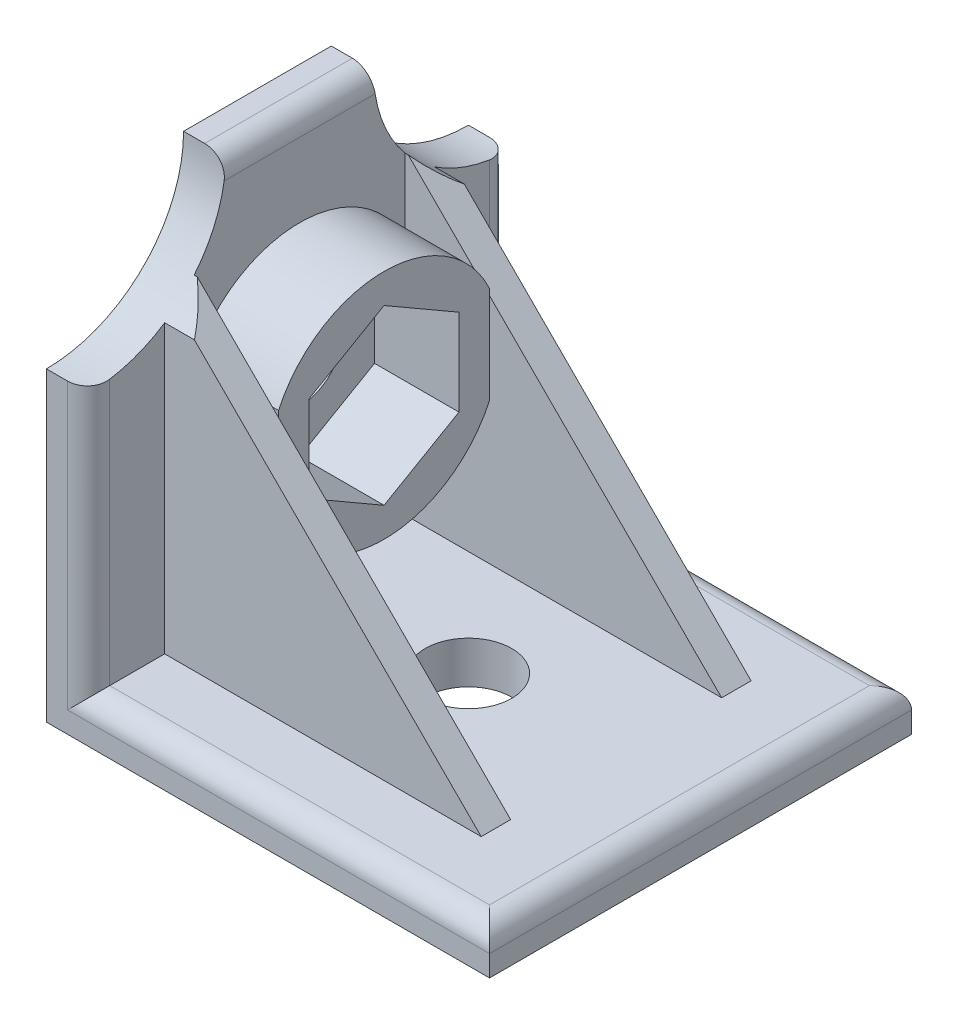
SolidWorks part; units mm, degrees
ref_plane "Plan de face" through (0, 0, 0) normal (0, 0, 1) x (1, 0, 0)
ref_plane "Plan de dessus" through (0, 0, 0) normal (0, 1, 0) x (1, 0, 0)
ref_plane "Plan de droite" through (0, 0, 0) normal (1, 0, 0) x (0, 0, -1)
sketch "Esquisse1" plane through (0, 0, 0) normal (0, 1, 0) x (1, 0, 0)
  line L1 (10.5, -10) -> (-10.5, -10)
  line L2 (10.5, -10) -> (10.5, 10)
  line L3 (10.5, 10) -> (-10.5, 10)
  line L4 (-10.5, -10) -> (-10.5, 10)
  line L5 (10.5, -10) -> (-10.5, 10) construction
  line L6 (10.5, 10) -> (-10.5, -10) construction
  point P0 (0, 0)
  dimension "D1" = 20
  dimension "D2" = 21
extrude "Boss.-Extru.1" add sketch "Esquisse1" along normal blind 2
sketch "Esquisse2" plane through (0, 2, 0) normal (0, 1, 0) x (1, 0, 0)
  line L0 (-8.5, 10) -> (-8.5, -10)
  line L4 (-10.5, 10) -> (-10.5, -10)
  line L5 (-10.5, -10) -> (10.5, -10)
  line L6 (10.5, -10) -> (10.5, 10)
  line L7 (10.5, 10) -> (-10.5, 10)
  line L8 (-10.5, 10) -> (-10.5, -10)
  line L9 (-10.5, -10) -> (10.5, -10)
  line L10 (10.5, -10) -> (10.5, 10)
  line L11 (10.5, 10) -> (-10.5, 10)
  line M6 (-10.5, 10) -> (-10.5, -10)
  line M7 (-10.5, -10) -> (10.5, -10)
  line M9 (10.5, 10) -> (-10.5, 10)
  dimension "D2" = 2
  dimension "D1" = 0
extrude "Boss.-Extru.2" add sketch "Esquisse2" along normal blind 19 contours L0 M9 M6 M7 region at (-9.5, 2, 0)
sketch "Esquisse3" plane through (0, 2, 0) normal (0, 1, 0) x (1, 0, 0)
  line L0 (-0.5, 10) -> (-0.5, -10) construction
  line L1 (10.5, 0) -> (-8.5, 0) construction
  line L4 (10.5, 10) -> (-8.5, 10)
  line L5 (-8.5, 10) -> (-8.5, -10)
  line L6 (-8.5, -10) -> (10.5, -10)
  line L7 (10.5, -10) -> (10.5, 10)
  line L8 (10.5, 10) -> (-8.5, 10)
  line L9 (-8.5, 10) -> (-8.5, -10)
  line L10 (-8.5, -10) -> (10.5, -10)
  line L11 (10.5, -10) -> (10.5, 10)
  circle A0 centre (-0.5, 0) radius 2.05
  dimension "D2" = 8
  dimension "D3" = 4.1
  dimension "D1" = 0
extrude "Enlèv. mat.-Extru.1" cut sketch "Esquisse3" against normal blind 20 contours A0
sketch "Esquisse4" plane through (-8.5, 0, 0) normal (1, 0, 0) x (0, 0, -1)
  line L0 (0, 21) -> (0, 2) construction
  line L1 (-10, 11) -> (10, 11) construction
  line L4 (-10, 2) -> (10, 2)
  line L5 (10, 2) -> (10, 21)
  line L6 (10, 21) -> (-10, 21)
  line L7 (-10, 21) -> (-10, 2)
  line L8 (-10, 2) -> (10, 2)
  line L9 (10, 2) -> (10, 21)
  line L10 (10, 21) -> (-10, 21)
  line L11 (-10, 21) -> (-10, 2)
  circle A0 centre (0, 11) radius 2.05
  dimension "D2" = 4.1
  dimension "D3" = 9
  dimension "D1" = 0
extrude "Enlèv. mat.-Extru.2" cut sketch "Esquisse4" against normal blind 20 contours A0
sketch "Esquisse5" plane through (0, 2, 0) normal (0, 1, 0) x (1, 0, 0)
  line L0 (6.5, 10) -> (6.5, -10) construction
  line L1 (-8.5, -5) -> (6.5, -5)
  line L2 (6.5, -5) -> (6.5, -6.3948)
  line L3 (6.5, -6.3948) -> (-8.5, -6.3948)
  line L4 (10.5, 10) -> (-8.5, 10)
  line L5 (-8.5, 10) -> (-8.5, -10)
  line L6 (-8.5, -10) -> (10.5, -10)
  line L7 (10.5, -10) -> (10.5, 10)
  line L8 (10.5, 10) -> (-8.5, 10)
  line L9 (-8.5, 10) -> (-8.5, -10)
  line L10 (-8.5, -10) -> (10.5, -10)
  line L11 (10.5, -10) -> (10.5, 10)
  line L12 (-8.5, 0) -> (10.5, 0) construction
  line L13 (6.5, 5) -> (6.5, 6.3948)
  line L14 (6.5, 6.3948) -> (-8.5, 6.3948)
  line L15 (-8.5, 5) -> (6.5, 5)
  line M11 (-8.5, 10) -> (-8.5, -10)
  dimension "D2" = 1.3948
  dimension "D3" = 15
  dimension "D4" = 5
  dimension "D1" = 0
extrude "Boss.-Extru.3" add sketch "Esquisse5" along normal blind 15 contours L3 L2 L1 M11 | L9 L15 L13 L14 region at (-1, 2, 5.6974) region at (-1, 2, -5.6974)
chamfer "Chanfrein1" distance 15 angle 45 2 edges at (6.5, 17, 5.6974) (6.5, 17, -5.6974)
fillet "Congé1" radius 1 6 edges at (1, 2, -10) (-8.5, 11.5, -10) (10.5, 2, 0) (1, 2, 10) (-8.5, 11.5, 10) (-8.5, 21, 0)
sketch "Esquisse7" plane through (-8.5, 0, 0) normal (1, 0, 0) x (0, 0, -1)
  line L0 (0, 0) -> (0, 11) construction
  line L1 (0, 6.9008) -> (3.55, 8.9504)
  line L2 (3.55, 8.9504) -> (3.55, 13.0496)
  line L3 (3.55, 13.0496) -> (0, 15.0992)
  line L4 (0, 15.0992) -> (-3.55, 13.0496)
  line L5 (-3.55, 13.0496) -> (-3.55, 8.9504)
  line L6 (-3.55, 8.9504) -> (0, 6.9008)
  line L12 (6.3948, 2) -> (9, 2)
  line L13 (9, 2) -> (9, 20)
  line L14 (9, 20) -> (-9, 20)
  line L15 (-9, 20) -> (-9, 2)
  line L16 (-9, 2) -> (-6.3948, 2)
  line L17 (-6.3948, 2) -> (-6.3948, 17)
  line L18 (-6.3948, 17) -> (-5, 17)
  line L19 (-5, 17) -> (-5, 2)
  line L20 (-5, 2) -> (5, 2)
  line L21 (5, 2) -> (5, 17)
  line L22 (5, 17) -> (6.3948, 17)
  line L23 (6.3948, 17) -> (6.3948, 2)
  line L24 (6.3948, 2) -> (9, 2)
  line L25 (9, 2) -> (9, 20)
  line L26 (9, 20) -> (-9, 20)
  line L27 (-9, 20) -> (-9, 2)
  line L28 (-9, 2) -> (-6.3948, 2)
  line L29 (-6.3948, 2) -> (-6.3948, 17)
  line L30 (-6.3948, 17) -> (-5, 17)
  line L31 (-5, 17) -> (-5, 2)
  line L32 (-5, 2) -> (5, 2)
  line L33 (5, 2) -> (5, 17)
  line L34 (5, 17) -> (6.3948, 17)
  line L35 (6.3948, 17) -> (6.3948, 2)
  circle A0 centre (0, 11) radius 2.05 construction
  circle A1 centre (0, 11) radius 2.05
  circle A2 centre (0, 11) radius 5.5 construction
  arc A3 (-5, 13.2913) -> (5, 13.2913) centre (0, 11) cw
  arc A4 (5, 8.7087) -> (-5, 8.7087) centre (0, 11) cw
  circle A5 centre (0, 11) radius 3.55 construction
  point P20 (-0.511, 6.9328)
  dimension "D2" = 11
  dimension "D3" = 7.1
  dimension "D1" = 0
extrude "Boss.-Extru.12" add sketch "Esquisse7" along normal blind 4 contours A4 L33 A3 L31 L6 L5 L4 L3 L2 L1 region at (-8.5, 11, -4.8513)
sketch "Esquisse9" plane through (0, 0, 0) normal (1, 0, 0) x (0, 0, -1)
  line L3 (-9, 20) -> (-10, 21)
  line L4 (-10, 21) -> (-9, 20)
  line L5 (-9, 20) -> (9, 20)
  line L6 (9, 20) -> (10, 21)
  line L7 (10, 21) -> (-10, 21)
  line L8 (-10, 21) -> (-9, 20)
  line L9 (-9, 20) -> (9, 20)
  line L10 (9, 20) -> (10, 21)
  line L11 (10, 21) -> (-10, 21)
  line L12 (-10, 21) -> (-10, 1)
  line L13 (-9, 2) -> (-9, 20)
  line L14 (-9, 20) -> (-10, 21)
  line L15 (-10, 21) -> (-10, 1)
  line L16 (-9, 2) -> (-9, 20)
  line L17 (10, 21) -> (9, 20)
  line L18 (9, 20) -> (9, 2)
  line L19 (10, 1) -> (10, 21)
  line L20 (10, 21) -> (9, 20)
  line L21 (9, 20) -> (9, 2)
  line L22 (10, 1) -> (10, 21)
  line L31 (5, 13.2913) -> (5, 17)
  line L32 (5, 17) -> (6.3948, 17)
  line L33 (6.3948, 17) -> (6.3948, 2)
  line L34 (6.3948, 2) -> (9, 2)
  line L35 (9, 2) -> (9, 20)
  line L36 (9, 20) -> (-9, 20)
  line L37 (-9, 20) -> (-9, 2)
  line L38 (-9, 2) -> (-6.3948, 2)
  line L39 (-6.3948, 2) -> (-6.3948, 17)
  line L40 (-6.3948, 17) -> (-5, 17)
  line L41 (-5, 17) -> (-5, 13.2913)
  line L42 (5, 13.2913) -> (5, 17)
  line L43 (5, 17) -> (6.3948, 17)
  line L44 (6.3948, 17) -> (6.3948, 2)
  line L45 (6.3948, 2) -> (9, 2)
  line L46 (9, 2) -> (9, 20)
  line L47 (9, 20) -> (-9, 20)
  line L48 (-9, 20) -> (-9, 2)
  line L49 (-9, 2) -> (-6.3948, 2)
  line L50 (-6.3948, 2) -> (-6.3948, 17)
  line L51 (-6.3948, 17) -> (-5, 17)
  line L52 (-5, 17) -> (-5, 13.2913)
  circle A0 centre (-10, 21) radius 6.5
  arc A1 (-9, 2) -> (-10, 1) centre (-9, 1) ccw
  arc A2 (-9, 2) -> (-10, 1) centre (-9, 1) ccw
  arc A3 (10, 1) -> (9, 2) centre (9, 1) ccw
  arc A4 (10, 1) -> (9, 2) centre (9, 1) ccw
  arc A5 (5, 13.2913) -> (-5, 13.2913) centre (0, 11) ccw
  arc A6 (5, 13.2913) -> (-5, 13.2913) centre (0, 11) ccw
  circle A7 centre (10, 21) radius 6.5
  dimension "D5" = 13
  dimension "D1" = 0
  dimension "D2" = 0
  dimension "D3" = 0
  dimension "D4" = 0
extrude "Enlèv. mat.-Extru.3" cut sketch "Esquisse9" against normal through all both and the other way through all contours L11 A0 L15 | L22 A7 L11 | L48 A0 L50 L51 L52 L9 | L15 A0 L48 L8 | L9 A0 L11 L8 | L11 A7 L9 L10 | L9 A7 L42 L43 L44 L21 | L21 A7 L22 L10 | A0 | A7 region at (0, 17.5198, 9.515) region at (0, 20.515, 6.5198) region at (0, 17.8809, 6.8594) region at (0, 21.9196, 10.9196) region at (0, 20.515, -6.5198) region at (0, 17.8809, -6.8594) region at (0, 21.9196, -10.9196) region at (0, 17.5198, -9.515)
